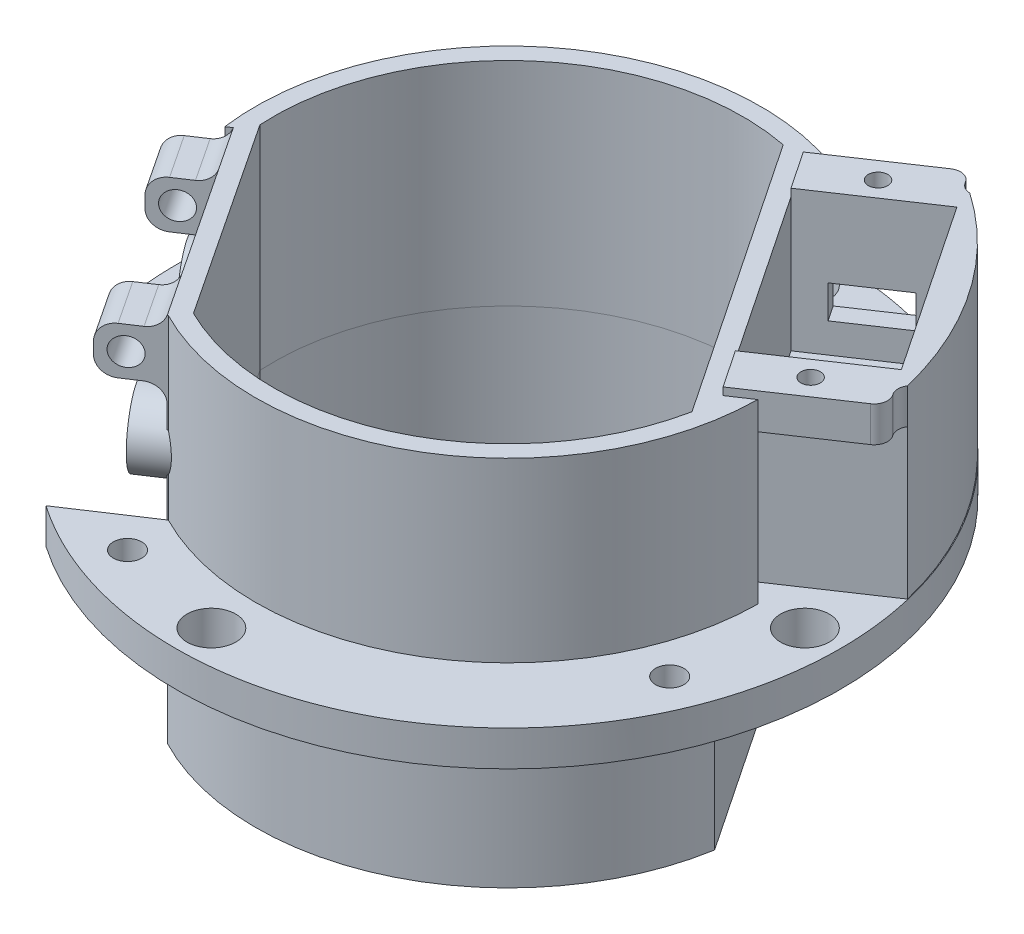
SolidWorks part; units mm, degrees
ref_plane "Front Plane" through (0, 0, 0) normal (0, 0, 1) x (1, 0, 0)
ref_plane "Top Plane" through (0, 0, 0) normal (0, 1, 0) x (1, 0, 0)
ref_plane "Right Plane" through (0, 0, 0) normal (1, 0, 0) x (0, 0, -1)
sketch "Sketch1" plane through (0, 0, 0) normal (0, 1, 0) x (1, 0, 0)
  circle A1 centre (0, 0) radius 37.5
  dimension "D1" = 75
extrude "Boss-Extrude1" add sketch "Sketch1" along normal blind 4
sketch "Sketch2" plane through (0, 4, 0) normal (0, 1, 0) x (1, 0, 0)
sketch "Sketch3" plane through (0, 4, 0) normal (0, 1, 0) x (1, 0, 0)
  line L0 (9.5768, 26.8428) -> (7.7196, 25.5977)
  line L1 (7.7196, 25.5977) -> (26.1515, -1.8954)
  line L2 (26.1515, -1.8954) -> (28.4982, -0.3222)
  line L3 (26.9944, -0.7284) -> (30.8983, 1.8888) construction
  line L4 (23.1422, 3.4912) -> (25.8151, -0.4957) construction
  line L5 (13.0232, 28.5514) -> (9.1193, 25.9342) construction
  line L6 (5.0297, 26.0183) -> (25.9789, -5.2295)
  line L7 (-25.7545, -6.2417) -> (-27.6753, -3.3396)
  line L8 (-25.7545, -6.2417) -> (-15.8097, -21.2674)
  line L9 (-25.156, -8.0519) -> (-16.7117, -20.8106) construction
  line L10 (-27.6753, -3.3396) -> (-28.2557, -3.7238)
  line L11 (-15.8097, -21.2674) -> (-13.0605, -25.4212)
  line L12 (-12.984, -25.3706) -> (-13.0605, -25.4212)
  line L13 (-15.9728, -27.1089) -> (-16.9735, -27.7712) construction
  line L14 (-30.3668, -5.3608) -> (-31.3675, -6.0231) construction
  line L15 (-26.454, -1.5611) -> (-11.7746, -23.7405)
  line L16 (-24.0867, -5.1379) -> (-14.1419, -20.1636) construction
  arc A0 (9.5768, 26.8428) -> (-28.2557, -3.7238) centre (0, 0) ccw
  arc A1 (5.0297, 26.0183) -> (-26.454, -1.5611) centre (0, 0) ccw
  arc A2 (-12.984, -25.3706) -> (28.4982, -0.3222) centre (0, 0) ccw
  circle A3 centre (0, 0) radius 28.5 construction
  circle A4 centre (0, 0) radius 26.5 construction
  arc A5 (-11.7746, -23.7405) -> (25.9789, -5.2295) centre (0, 0) ccw
  point P1 (26.5, 0)
  point P5 (27.2547, 8.3326)
  point P29 (-16.4731, -27.4401)
  dimension "D1" = 57
  dimension "D3" = 0.5
  dimension "D4" = 0.5
  dimension "D5" = 0.5
  dimension "D6" = 2
  dimension "D7" = 0.5
  dimension "D8" = 0.2
  dimension "D9" = 0.2
  dimension "D2" = 2
  dimension "D10" = 2
extrude "Boss-Extrude2" add sketch "Sketch3" along normal blind 20
sketch "Sketch5" plane through (0, 4, 0) normal (0, 1, 0) x (1, 0, 0)
  line L0 (0, 0) -> (-12.1624, 0) construction
  line L1 (0, 0) -> (-12.362, -30.5971) construction
  circle A0 centre (-33.4949, 0.0001) radius 2.75
  circle A1 centre (-0.0001, 33.4948) radius 2.75
  circle A2 centre (33.4945, 0) radius 2.75
  circle A3 centre (-0.0003, -33.4947) radius 2.75
  circle A4 centre (-12.362, -30.5971) radius 1.6
  circle A5 centre (-30.5971, 12.362) radius 1.6
  circle A6 centre (12.362, 30.5971) radius 1.6
  circle A7 centre (30.5971, -12.362) radius 1.6
  point P12 (-0.0002, 0.0001)
  point P24 (0, 0)
  dimension "D1" = 5.5
  dimension "D5" = 3.2
  dimension "D3" = 33
  dimension "D4" = 68
  dimension "D2" = 4
  dimension "D6" = 4
extrude "Cut-Extrude2" cut sketch "Sketch5" against normal blind 10
sketch "Sketch6" plane through (0, 4, 0) normal (0, 1, 0) x (1, 0, 0)
  line L0 (18.5052, 32.5947) -> (37.1734, 4.7492) construction
sketch "Sketch7" plane through (17.1655, 0, -11.5081) normal (0.8306, 0, -0.5569) x (-0.5569, 0, -0.8306)
  line L0 (-11.037, 24.85) -> (-11.037, 8.95)
  line L1 (-11.037, 8.95) -> (11.863, 8.95)
  line L2 (11.863, 8.95) -> (11.863, 24.85)
  line L3 (11.863, 24.85) -> (16.963, 24.85)
  line L4 (-11.037, 24.85) -> (-16.137, 24.85)
  line L5 (-16.137, 24.85) -> (-16.137, 20.85)
  line L7 (16.963, 20.85) -> (16.963, 24.85)
  line L8 (-16.137, 20.85) -> (-13.137, 20.85)
  line L9 (-13.137, 20.85) -> (-13.137, 4)
  line L10 (16.963, 20.85) -> (13.963, 20.85)
  line L11 (13.963, 20.85) -> (13.963, 4)
  line L12 (-13.137, 4) -> (13.963, 4)
  line L13 (-7.1851, 9.15) -> (-6.6299, 9.15) construction
  line L14 (-10.837, 9.35) -> (-10.837, 14.65) construction
  line L15 (11.663, 9.35) -> (11.663, 14.65) construction
  line L17 (-15.637, 24.95) -> (-14.787, 24.95) construction
  line L18 (-14.787, 24.95) -> (15.613, 24.95) construction
  line L19 (16.963, 24) -> (16.963, 4) construction
  line L20 (-16.137, 24) -> (-16.137, 4) construction
  point P17 (0.413, 4)
  dimension "D1" = 0.2
  dimension "D2" = 0.2
  dimension "D3" = 0.2
  dimension "D5" = 0.1
  dimension "D6" = 0.1
  dimension "D7" = 3
  dimension "D8" = 4
  dimension "D9" = 3
extrude "Boss-Extrude3" add sketch "Sketch7" along normal blind 13.5
sketch "Sketch8" plane through (0, 4, 0) normal (0, 1, 0) x (1, 0, 0)
  line L0 (35.6942, 8.1139) -> (20.6034, 30.6234)
  line L1 (20.6034, 30.6234) -> (21.1307, 30.977)
  line L2 (35.6942, 8.1139) -> (36.4519, 8.6219)
  arc A1 (36.4519, 8.6219) -> (21.1307, 30.977) centre (-0.6007, -0.3445) ccw
extrude "Boss-Extrude4" add sketch "Sketch8" along normal up to surface (20.85 mm away) up to face at (30.3382, 24.85, -3.9814)
fillet "Fillet2" radius 1.5 4 edges at (18.9328, 22.85, -33.1153) (20.6034, 22.85, -30.6234) (37.3647, 22.85, -5.6221) (35.6942, 22.85, -8.1139)
fillet "Fillet3" radius 1.5 4 edges at (26.1515, 12.425, 1.8954) (24.481, 12.425, -0.5964) (9.3902, 12.425, -23.1059) (7.7196, 12.425, -25.5977)
sketch "Sketch9" plane through (0, 24.85, 0) normal (0, 1, 0) x (1, 0, 0)
  circle A0 centre (14.6773, 27.0718) radius 1.1
  circle A1 centre (30.1579, 3.9809) radius 1.1
extrude "Cut-Extrude3" cut sketch "Sketch9" against normal blind 3.5
sketch "Sketch10" plane through (-7.7754, 0, -11.5978) normal (-0.5569, 0, -0.8306) x (-0.8306, 0, 0.5569)
  line L1 (-30.8445, 16.0062) -> (-23.6879, 16.0062)
  line L2 (-30.8445, 16.0062) -> (-30.8445, 12.2938)
  line L3 (-30.8445, 12.2938) -> (-23.6879, 12.2938)
  line L4 (-23.6879, 16.0062) -> (-23.6879, 12.2938)
  line L5 (-30.8445, 16.0062) -> (-23.6879, 12.2938) construction
  line L6 (-30.8445, 12.2938) -> (-23.6879, 16.0062) construction
  point P0 (-27.2662, 14.15)
extrude "Cut-Extrude4" cut sketch "Sketch10" against normal blind 2.5
sketch "Sketch11" plane through (0, 4, 0) normal (0, 1, 0) x (1, 0, 0)
  line L0 (-27.6753, -3.3396) -> (-41.2104, -12.2979)
  line L1 (-41.2104, -12.2979) -> (-26.5957, -34.3795)
  line L2 (-13.0605, -25.4212) -> (-26.5957, -34.3795)
  line L5 (-27.6753, -3.3396) -> (-13.0605, -25.4212)
  line L6 (-27.6753, -3.3396) -> (-13.0605, -25.4212)
  dimension "D1" = 0
extrude "Cut-Extrude5" cut sketch "Sketch11" against normal blind 5.5
sketch "Sketch12" plane through (-20.7821, 0, 13.7546) normal (-0.8339, 0, 0.5519) x (0.5519, 0, 0.8339)
  circle A0 centre (-9.6896, 10.6001) radius 4
  circle A1 centre (10.6504, 10.6001) radius 4
  dimension "D1" = 8
  dimension "D2" = 8
extrude "Boss-Extrude5" add sketch "Sketch12" along normal blind 4 from offset 0.8 offset against normal yes
sketch "Sketch13" plane through (-23.4505, 0, 15.5208) normal (-0.8339, 0, 0.5519) x (0.5519, 0, 0.8339)
  circle A0 centre (-9.6896, 10.6001) radius 2.1
  circle A1 centre (10.6504, 10.6001) radius 2.1
  dimension "D1" = 4.2
  dimension "D2" = 4.2
extrude "Cut-Extrude6" cut sketch "Sketch13" against normal blind 4
sketch "Sketch14" plane through (0, 4, 0) normal (0, 1, 0) x (1, 0, 0)
  line L6 (25.9789, -5.2295) -> (5.0297, 26.0183)
  line L7 (-26.454, -1.5611) -> (-11.7746, -23.7405)
  line L8 (25.9789, -5.2295) -> (5.0297, 26.0183)
  line L9 (-26.454, -1.5611) -> (-11.7746, -23.7405)
  arc A9 (-11.7746, -23.7405) -> (25.9789, -5.2295) centre (0, 0) ccw
  arc A10 (5.0297, 26.0183) -> (-26.454, -1.5611) centre (0, 0) ccw
  arc A11 (-11.7746, -23.7405) -> (25.9789, -5.2295) centre (0, 0) ccw
  arc A12 (5.0297, 26.0183) -> (-26.454, -1.5611) centre (0, 0) ccw
  dimension "D1" = 0
extrude "Cut-Extrude7" cut sketch "Sketch14" against normal blind 10
sketch "Sketch15" plane through (0, 0, 0) normal (0, -1, 0) x (1, 0, 0)
  line L4 (6.237, -27.8092) -> (28.0941, 4.793)
  line L5 (-13.1511, 25.2843) -> (-28.413, 2.2249)
  arc A6 (28.0941, 4.793) -> (-13.1511, 25.2843) centre (0, 0) ccw
  arc A7 (-28.413, 2.2249) -> (6.237, -27.8092) centre (0, 0) ccw
extrude "Boss-Extrude6" add sketch "Sketch15" along normal blind 18 separate body
shell "Shell1" thickness 2 removed face at (-2.4007, 0, 1.5586)
ref_plane "Plane1" through (-20.6969, 0, -31.2712) normal (-0.5519, 0, -0.8339) x (-0.8339, 0, 0.5519)
sketch "Sketch17" plane through (-20.7821, 0, 13.7546) normal (-0.8339, 0, 0.5519) x (0.5519, 0, 0.8339)
  line L0 (-12.4896, 24) -> (-12.4896, 13.4566) construction
  line L1 (-12.4896, 17.3215) -> (-6.6044, 17.3215)
  line L2 (-12.4896, 17.3215) -> (-12.4896, 22.6586)
  line L3 (-12.4896, 22.6586) -> (-6.6044, 22.6586)
  line L4 (-6.6044, 17.3215) -> (-6.6044, 22.6586)
  line L5 (0.7504, 24) -> (0.7504, 18.5531) construction
  line L6 (-12.4896, 24) -> (13.9904, 24) construction
  line L7 (8.1052, 17.3215) -> (8.1052, 22.6586)
  line L8 (13.9904, 22.6586) -> (8.1052, 22.6586)
  line L9 (13.9904, 17.3215) -> (13.9904, 22.6586)
  line L10 (13.9904, 17.3215) -> (8.1052, 17.3215)
extrude "Boss-Extrude7" add sketch "Sketch17" along normal blind 6
sketch "Sketch18" plane through (-6.8932, 0, -10.415) normal (-0.5519, 0, -0.8339) x (-0.8339, 0, 0.5519)
  circle A0 centre (28.2696, 19.99) radius 1.55
  dimension "D1" = 3.1
extrude "Cut-Extrude8" cut sketch "Sketch18" against normal blind 47
fillet "Fillet4" radius 2 8 edges at (-14.6846, 22.6586, 22.9674) (-14.6846, 17.3215, 22.9674) (-19.688, 17.3215, 26.2789) (-19.688, 22.6586, 26.2789) (-26.0512, 17.3215, 5.7934) (-26.0512, 22.6586, 5.7934) (-31.0546, 17.3215, 9.1049) (-31.0546, 22.6586, 9.1049)
